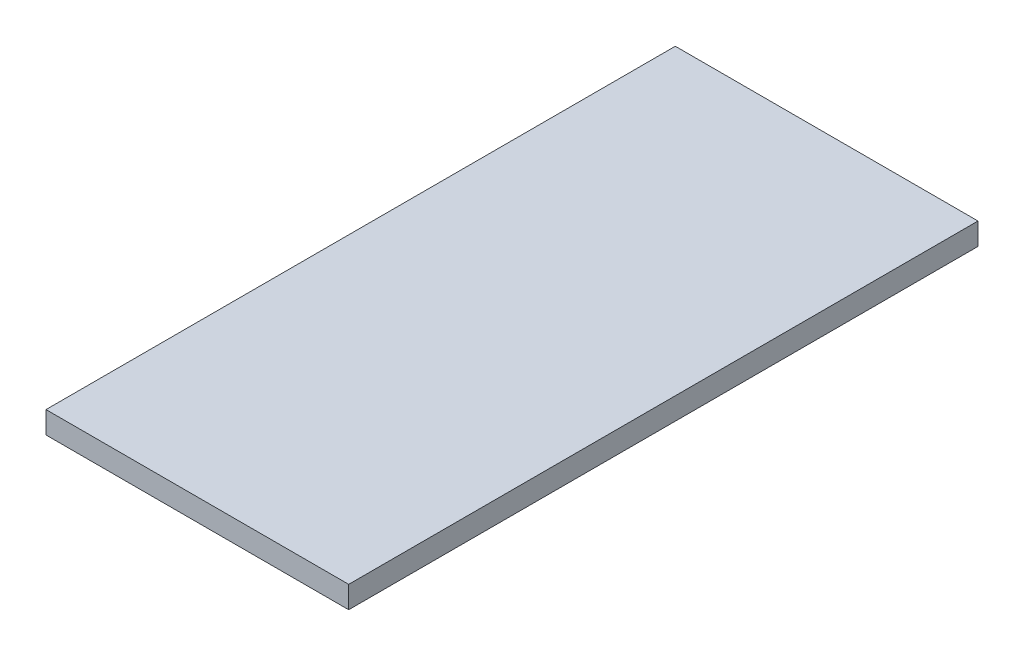
SolidWorks part; units mm, degrees
ref_plane "前视基准面" through (0, 0, 0) normal (0, 0, 1) x (1, 0, 0)
ref_plane "上视基准面" through (0, 0, 0) normal (0, 1, 0) x (1, 0, 0)
ref_plane "右视基准面" through (0, 0, 0) normal (1, 0, 0) x (0, 0, -1)
other "Configuration Table"
sketch "草图1" plane through (0, 0, 0) normal (0, 1, 0) x (1, 0, 0)
  line L5 (-11.5, -40) -> (11.5, -40)
  line L6 (-11.5, -40) -> (-11.5, 40)
  line L15 (-11.5, 40) -> (11.5, 40)
  line L16 (11.5, -40) -> (11.5, 40)
  line L17 (-11.5, -40) -> (11.5, 40) construction
  line L18 (-11.5, 40) -> (11.5, -40) construction
  line L19 (-9.5, -38) -> (9.5, -38)
  line L20 (-9.5, -38) -> (-9.5, 38)
  line L21 (-9.5, 38) -> (9.5, 38)
  line L22 (9.5, -38) -> (9.5, 38)
  line L23 (-9.5, -38) -> (9.5, 38) construction
  line L24 (-9.5, 38) -> (9.5, -38) construction
  point P0 (0, 0)
  point P5 (0, 0)
  dimension "D1" = 23
  dimension "D2" = 80
  dimension "D3" = 76
  dimension "D4" = 19
extrude "凸台-拉伸1" add sketch "草图1" along normal blind 7 contours L15 L16 L5 L6
extrude "切除-拉伸2" cut sketch "草图1<5>" along normal blind 3 contours L20 L21 L22 L19
sketch "草图1<5>" plane through (0, 0, 0) normal (0, 1, 0) x (1, 0, 0) same geometry as "草图1"
sketch "草图2" plane through (0, 3, 0) normal (0, -1, 0) x (1, 0, 0)
  circle A0 centre (-6, 34.5802) radius 0.75
  circle A1 centre (6, 34.5802) radius 0.75
  circle A2 centre (6, 18.5802) radius 0.75
  circle A3 centre (-6, 18.5802) radius 0.75
  circle A4 centre (-6, 8) radius 0.75
  circle A5 centre (6, 8) radius 0.75
  circle A6 centre (6, -8) radius 0.75
  circle A7 centre (-6, -8) radius 0.75
  circle A8 centre (-6, -18.5802) radius 0.75
  circle A9 centre (6, -18.5802) radius 0.75
  circle A10 centre (6, -34.5802) radius 0.75
  circle A11 centre (-6, -34.5802) radius 0.75
  dimension "D1" = 1.5
extrude "切除-拉伸3" cut sketch "草图2" against normal blind 2
sketch "草图4" plane through (0, 7, 0) normal (0, 1, 0) x (1, 0, 0)
  line L0 (-11.5, 40) -> (11.5, 40) construction
  line L1 (-39, 120) -> (57.2, 120)
  line L2 (-39, 120) -> (-39, 40)
  line L3 (-39, 40) -> (57.2, 40)
  line L4 (57.2, 120) -> (57.2, 40)
  dimension "D1" = 80
  dimension "D2" = 39
  dimension "D3" = 57.2
extrude "凸台-拉伸2" add sketch "草图4" against normal up to surface (7 mm away) up to face at (0, 0, 0)
sketch "草图5" plane through (0, 0, 0) normal (0, -1, 0) x (1, 0, 0)
  line L0 (57.2, -120) -> (-39, -120) construction
  line L1 (-35.8, -118.2) -> (-6.4, -118.2)
  line L2 (-35.8, -118.2) -> (-35.8, -75.8)
  line L3 (-35.8, -75.8) -> (-6.4, -75.8)
  line L4 (-6.4, -118.2) -> (-6.4, -75.8)
  line L5 (43, -79) -> (55.4, -79)
  line L6 (43, -79) -> (43, -115)
  line L7 (43, -115) -> (55.4, -115)
  line L8 (55.4, -79) -> (55.4, -115)
  line L9 (-39, -120) -> (-39, -40) construction
  line L10 (57.2, -40) -> (57.2, -120) construction
  dimension "D1" = 1.8
  dimension "D2" = 3.2
  dimension "D3" = 29.4
  dimension "D4" = 42.4
  dimension "D5" = 5
  dimension "D6" = 1.8
  dimension "D7" = 12.4
  dimension "D8" = 36
extrude "切除-拉伸4" cut sketch "草图5" against normal blind 3
sketch "草图6" plane through (0, 3, 0) normal (0, -1, 0) x (1, 0, 0)
  line L0 (-16.1, -78.5) -> (-9.1, -83.5) construction
  line L2 (-9.1, -110.5) -> (-16.1, -115.5) construction
  line L4 (43, -115) -> (55.4, -115) construction
  line L5 (-31.1, -78.5) -> (-31.1, -75.8) construction
  line L6 (-35.8, -75.8) -> (-35.8, -118.2) construction
  line L7 (-6.4, -75.8) -> (-35.8, -75.8) construction
  line L8 (-31.1, -115.5) -> (-31.1, -118.2) construction
  line L9 (49.2, -81.7267) -> (49.2, -79) construction
  line L10 (55.4, -79) -> (43, -79) construction
  line L11 (49.2, -112.2733) -> (49.2, -115) construction
  line L12 (49.2, -81.7267) -> (49.2, -112.2733) construction
  line L13 (46.2, -97) -> (49.2, -97) construction
  line L14 (-35.8, -118.2) -> (-6.4, -118.2) construction
  circle A0 centre (-31.1, -78.5) radius 0.65
  circle A1 centre (-16.1, -78.5) radius 0.65
  circle A2 centre (-31.1, -115.5) radius 0.65
  circle A3 centre (-16.1, -115.5) radius 0.65
  circle A4 centre (49.2, -112.2733) radius 0.65
  circle A5 centre (46.2, -97) radius 0.65
  circle A6 centre (49.2, -81.7267) radius 0.65
  circle A7 centre (-9.1, -110.5) radius 0.65
  circle A8 centre (-9.1, -83.5) radius 0.65
  dimension "D1" = 1.3
  dimension "D2" = 15
  dimension "D3" = 7
  dimension "D5" = 4.7
  dimension "D6" = 37
  dimension "D7" = 27
  dimension "D8" = 30.5465
  dimension "D9" = 3
extrude "切除-拉伸5" cut sketch "草图6" against normal blind 2
sketch "草图8" plane through (0, 0, -120) normal (0, 0, -1) x (-1, 0, 0)
  line L0 (-57.2, 0) -> (-57.2, 7) construction
  line L1 (-57.2, 7) -> (39, 7)
  line L2 (-57.2, 7) -> (-57.2, 0)
  line L3 (-57.2, 0) -> (39, 0)
  line L4 (39, 7) -> (39, 0)
  line L5 (-57.2, 0) -> (39, 0) construction
extrude "凸台-拉伸3" add sketch "草图8" along normal blind 40
sketch "草图15" plane through (0, 0, 0) normal (0, -1, 0) x (1, 0, 0)
  line L0 (-11.5, 40) -> (-11.5, -40) construction
  line L1 (-11.5, -40) -> (-39, -40)
  line L2 (-11.5, -40) -> (-11.5, 40)
  line L3 (-11.5, 40) -> (-39, 40)
  line L4 (-39, -40) -> (-39, 40)
  line L5 (-39, -160) -> (-39, -40) construction
  line L6 (-11.5, 40) -> (11.5, 40) construction
  line L7 (11.5, -40) -> (57.2, -40) construction
  line L8 (11.5, -40) -> (57.2, -40)
  line L9 (11.5, -40) -> (11.5, 40)
  line L10 (11.5, 40) -> (57.2, 40)
  line L11 (57.2, -40) -> (57.2, 40)
  line L12 (11.5, 40) -> (11.5, -40) construction
  line L13 (57.2, -40) -> (57.2, -160) construction
extrude "凸台-拉伸4" add sketch "草图15" against normal through all
sketch "草图9" plane through (0, 0, 0) normal (0, -1, 0) x (1, 0, 0)
  line L0 (55.4, -115) -> (55.4, -79) construction
  line L1 (55.4, -121.8) -> (-2.8, -121.8)
  line L2 (55.4, -121.8) -> (55.4, -158)
  line L3 (55.4, -158) -> (-2.8, -158)
  line L4 (-2.8, -121.8) -> (-2.8, -158)
  line L5 (57.2, -160) -> (-39, -160) construction
  dimension "D1" = 36.2
  dimension "D2" = 2
  dimension "D3" = 58.2
extrude "切除-拉伸6" cut sketch "草图9" against normal blind 1
sketch "草图10" plane through (0, 1, 0) normal (0, -1, 0) x (1, 0, 0)
  line L0 (55.4, -158) -> (55.4, -121.8) construction
  line L1 (15.7, -126.6) -> (17.4, -126.6)
  line L2 (15.7, -126.6) -> (15.7, -153.2)
  line L3 (15.7, -153.2) -> (17.4, -153.2)
  line L4 (17.4, -126.6) -> (17.4, -153.2)
  line L5 (28, -127.4) -> (33.2, -127.4)
  line L6 (28, -127.4) -> (28, -152.4)
  line L7 (28, -152.4) -> (33.2, -152.4)
  line L8 (33.2, -127.4) -> (33.2, -152.4)
  line L9 (39.4, -125.8) -> (47.5, -125.8)
  line L10 (39.4, -125.8) -> (39.4, -154)
  line L11 (39.4, -154) -> (47.5, -154)
  line L12 (47.5, -125.8) -> (47.5, -154)
  line L13 (52.3, -129.8) -> (55.4, -129.8)
  line L14 (52.3, -129.8) -> (52.3, -150)
  line L15 (52.3, -150) -> (55.4, -150)
  line L16 (55.4, -129.8) -> (55.4, -150)
  line L17 (53.85, -129.8) -> (53.85, -121.8) construction
  line L18 (55.4, -121.8) -> (-2.8, -121.8) construction
  line L19 (53.85, -150) -> (53.85, -158) construction
  line L20 (-2.8, -158) -> (55.4, -158) construction
  line L21 (43.45, -125.8) -> (43.45, -121.8) construction
  line L22 (43.45, -154) -> (43.45, -158) construction
  line L23 (30.6, -127.4) -> (30.6, -121.8) construction
  line L24 (30.6, -152.4) -> (30.6, -158) construction
  line L26 (16.55, -121.8) -> (16.55, -126.6) construction
  line L27 (16.55, -153.2) -> (16.55, -158) construction
  dimension "D1" = 3.1
  dimension "D2" = 20.2
  dimension "D3" = 4.8
  dimension "D4" = 8.1
  dimension "D5" = 28.2
  dimension "D6" = 22.2
  dimension "D7" = 5.2
  dimension "D8" = 25
  dimension "D9" = 38
  dimension "D10" = 1.7
  dimension "D11" = 26.6
extrude "切除-拉伸7" cut sketch "草图10" against normal blind 2
sketch "草图11" plane through (0, 1, 0) normal (0, -1, 0) x (1, 0, 0)
  line L0 (-2.8, -121.8) -> (-2.8, -158) construction
  line L2 (55.4, -121.8) -> (-2.8, -121.8) construction
  line L3 (-2.8, -158) -> (55.4, -158) construction
  line L4 (55.4, -158) -> (55.4, -121.8) construction
  circle A4 centre (0.3, -124.9) radius 0.65
  circle A5 centre (0.3, -154.9) radius 0.65
  circle A6 centre (52.3, -154.9) radius 0.65
  circle A7 centre (52.3, -124.9) radius 0.65
  dimension "D1" = 1.3
  dimension "D2" = 3.1
  dimension "D3" = 3.1
  dimension "D4" = 3.1
  dimension "D5" = 3.1
extrude "切除-拉伸8" cut sketch "草图11" against normal blind 2
sketch "草图12" plane through (0, 0, 0) normal (0, -1, 0) x (1, 0, 0)
  line L1 (-0.4, -88) -> (16, -88)
  line L2 (-0.4, -88) -> (-0.4, -118.2)
  line L3 (-0.4, -118.2) -> (16, -118.2)
  line L4 (16, -88) -> (16, -118.2)
  line L5 (-35.8, -118.2) -> (-6.4, -118.2) construction
  line L6 (-6.4, -118.2) -> (-6.4, -75.8) construction
  dimension "D1" = 16.4
  dimension "D2" = 30.2
  dimension "D3" = 6
extrude "切除-拉伸9" cut sketch "草图12" against normal blind 1.7
sketch "草图13" plane through (0, 0, 0) normal (0, -1, 0) x (1, 0, 0)
  line L0 (-0.4, -118.2) -> (16, -118.2) construction
  line L1 (20, -86) -> (39, -86)
  line L2 (20, -86) -> (20, -118.2)
  line L3 (20, -118.2) -> (39, -118.2)
  line L4 (39, -86) -> (39, -118.2)
  line L5 (16, -118.2) -> (16, -88) construction
  dimension "D1" = 32.2
  dimension "D2" = 19
  dimension "D3" = 4
extrude "切除-拉伸10" cut sketch "草图13" against normal blind 4.4
sketch "草图14" plane through (0, 0, 0) normal (0, -1, 0) x (1, 0, 0)
  line L0 (55.4, -115) -> (55.4, -79) construction
  line L1 (39.1, -47.7) -> (55.4, -47.7)
  line L2 (39.1, -47.7) -> (39.1, -73)
  line L3 (39.1, -73) -> (55.4, -73)
  line L4 (55.4, -47.7) -> (55.4, -73)
  line L5 (55.4, -79) -> (43, -79) construction
  point P8 (49.2, -79)
  dimension "D1" = 25.3
  dimension "D2" = 16.3
  dimension "D3" = 6
extrude "切除-拉伸11" cut sketch "草图14" against normal blind 1.7
sketch "草图16" plane through (0, 0, 0) normal (0, -1, 0) x (1, 0, 0)
  line L0 (-0.4, -118.2) -> (16, -118.2) construction
  line L1 (2.6, -118.2) -> (13, -118.2)
  line L2 (2.6, -118.2) -> (2.6, -121.8)
  line L3 (2.6, -121.8) -> (13, -121.8)
  line L4 (13, -118.2) -> (13, -121.8)
  line L5 (55.4, -121.8) -> (-2.8, -121.8) construction
  line L6 (20, -118.2) -> (39, -118.2) construction
  line L7 (23, -118.2) -> (36, -118.2)
  line L8 (23, -118.2) -> (23, -121.8)
  line L9 (23, -121.8) -> (36, -121.8)
  line L10 (36, -118.2) -> (36, -121.8)
  line L11 (39, -86) -> (20, -86) construction
  line L12 (23, -86) -> (36, -86)
  line L13 (23, -86) -> (23, -74)
  line L14 (23, -74) -> (36, -74)
  line L15 (36, -86) -> (36, -74)
  line L16 (39.1, -73) -> (55.4, -73) construction
  line L17 (42.1, -73) -> (52.4, -73)
  line L18 (42.1, -73) -> (42.1, -78)
  line L19 (42.1, -78) -> (52.4, -78)
  line L20 (52.4, -73) -> (52.4, -78)
  line L21 (55.4, -79) -> (43, -79) construction
  line L22 (16, -88) -> (-0.4, -88) construction
  line L23 (36, -74) -> (42.1, -74)
  line L24 (36, -74) -> (36, -78)
  line L25 (36, -78) -> (42.1, -78)
  line L26 (42.1, -74) -> (42.1, -78)
  line L27 (2.6, -88) -> (13, -88)
  line L28 (2.6, -88) -> (2.6, -74)
  line L29 (2.6, -74) -> (13, -74)
  line L30 (13, -88) -> (13, -74)
  line L31 (-0.4, -88) -> (-0.4, -118.2) construction
  line L32 (13, -74) -> (23, -74)
  line L33 (13, -74) -> (13, -78)
  line L34 (13, -78) -> (23, -78)
  line L35 (23, -74) -> (23, -78)
  line L36 (2.6, -88) -> (13, -88)
  line L37 (2.6, -88) -> (2.6, -118.2)
  line L38 (2.6, -118.2) -> (13, -118.2)
  line L39 (13, -88) -> (13, -118.2)
  line L40 (23, -86) -> (36, -86)
  line L41 (23, -86) -> (23, -118.2)
  line L42 (23, -118.2) -> (36, -118.2)
  line L43 (36, -86) -> (36, -118.2)
  line L44 (16, -118.2) -> (16, -88) construction
  line L45 (20, -86) -> (20, -118.2) construction
  line L46 (39, -118.2) -> (39, -86) construction
  line L49 (55.4, -73) -> (55.4, -47.7) construction
  line L50 (39.1, -47.7) -> (39.1, -73) construction
  line L51 (-2.8, -158) -> (55.4, -158) construction
  line L52 (2.6, -121.8) -> (13, -121.8)
  line L53 (2.6, -121.8) -> (2.6, -158)
  line L54 (2.6, -158) -> (13, -158)
  line L55 (13, -121.8) -> (13, -158)
  line L56 (55.4, -158) -> (55.4, -121.8) construction
  line L57 (55.4, -129.8) -> (13, -129.8)
  line L58 (55.4, -129.8) -> (55.4, -150)
  line L59 (55.4, -150) -> (13, -150)
  line L60 (13, -129.8) -> (13, -150)
  line L61 (55.4, -129.8) -> (52.3, -129.8) construction
  line L62 (52.3, -150) -> (55.4, -150) construction
  point P70 (0, 0)
  line M31 (55.4, -73) -> (39.1, -73)
  line M33 (20, -86) -> (39, -86)
  line M35 (39, -118.2) -> (20, -118.2)
  line M37 (-0.4, -88) -> (16, -88)
  line M39 (16, -118.2) -> (-0.4, -118.2)
  line M40 (55.4, -121.8) -> (55.4, -158)
  line M41 (55.4, -158) -> (-2.8, -158)
  line M43 (-2.8, -121.8) -> (55.4, -121.8)
  dimension "D1" = 3
  dimension "D2" = 3
  dimension "D3" = 3
  dimension "D4" = 3
  dimension "D5" = 1
  dimension "D6" = 1
  dimension "D7" = 3
  dimension "D8" = 3
extrude "切除-拉伸12" cut sketch "草图16" along direction (0, 1, 0) on the side against the normal blind 6 contours L30 L29 L28 M37 | L30 L34 L13 L32 | L15 L14 L13 M33 | L15 L25 L18 L23 | L20 L18 L19 M31 | L43 L41 M33 M35 | L39 L37 M37 M39 | L4 L2 M39 M43 | L10 L8 M35 M43 | L55 L53 M43 M41 | L59 L57 L55 M40 region at (7.8, 0, -103.1) region at (7.8, 0, -120) region at (7.8, 0, -139.9) region at (7.8, 0, -81) region at (34.2, 0, -139.9) region at (29.5, 0, -120) region at (18, 0, -76) region at (29.5, 0, -102.1) region at (29.5, 0, -80) region at (39.05, 0, -76) region at (47.25, 0, -75.5)
sketch "草图17" plane through (0, 0, 0) normal (0, -1, 0) x (1, 0, 0)
  line L0 (2.6, -74) -> (42.1, -74) construction
  line L1 (2.6, -88) -> (2.6, -74) construction
  line L2 (-0.4, -88) -> (-0.4, -118.2) construction
  line L3 (-0.4, -118.2) -> (2.6, -118.2) construction
  line L4 (39, -118.2) -> (39, -86) construction
  line L5 (39.1, -47.7) -> (39.1, -73) construction
  line L6 (2.6, -88) -> (-0.4, -88) construction
  line L7 (13, -82) -> (18, -82) construction
  line L8 (13, -88) -> (13, -78) construction
  line L9 (18, -82) -> (23, -82) construction
  line L10 (23, -86) -> (23, -78) construction
  line L11 (13, -78) -> (23, -78) construction
  line L12 (36, -82) -> (39.5, -82) construction
  line L14 (39.5, -82) -> (43, -82) construction
  line L16 (36, -86) -> (36, -78) construction
  line L17 (43, -79) -> (43, -115) construction
  line L18 (53.9, -73) -> (53.9, -79) construction
  line L19 (52.4, -73) -> (55.4, -73) construction
  line L20 (55.4, -79) -> (43, -79) construction
  line L21 (53.9, -76) -> (54.8, -76) construction
  line L22 (52.4, -76) -> (54.8, -76) construction
  line L23 (52.4, -73) -> (52.4, -78) construction
  line L24 (54.8, -76) -> (57.2, -76) construction
  line L25 (57.2, 40) -> (57.2, -160) construction
  circle A0 centre (-3.4, -117.2) radius 0.65
  circle A1 centre (41, -117.2) radius 0.65
  circle A2 centre (-0.4, -85) radius 0.65
  circle A3 centre (5.6, -71) radius 0.65
  circle A4 centre (36.1, -71) radius 0.65
  circle A5 centre (18, -82) radius 0.65
  circle A6 centre (39.5, -82) radius 0.65
  circle A7 centre (54.8, -76) radius 0.65
  dimension "D7" = 1.3
  dimension "D1" = 3
  dimension "D2" = 3
  dimension "D3" = 3
  dimension "D4" = 3
  dimension "D5" = 1
  dimension "D6" = 2
  dimension "D8" = 3
  dimension "D9" = 3
  dimension "D10" = 4
extrude "切除-拉伸13" cut sketch "草图17" against normal blind 3
